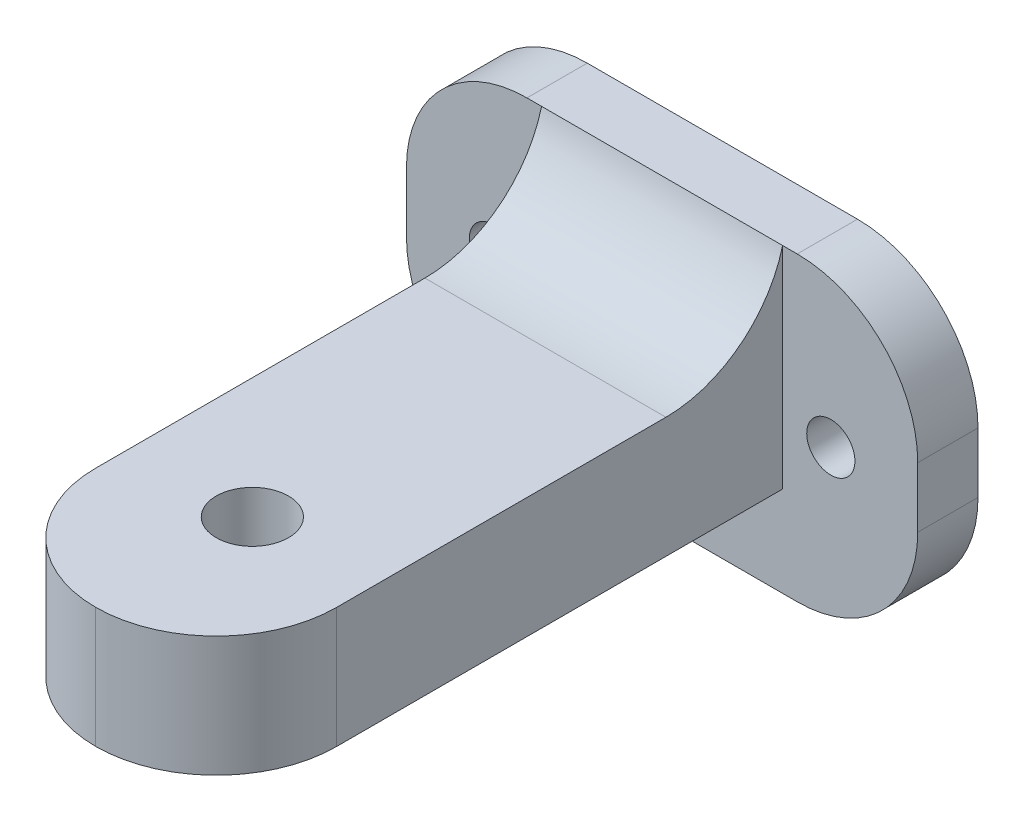
SolidWorks part; units mm, degrees
ref_plane "Front Plane" through (0, 0, 0) normal (0, 0, 1) x (1, 0, 0)
ref_plane "Top Plane" through (0, 0, 0) normal (0, 1, 0) x (1, 0, 0)
ref_plane "Right Plane" through (0, 0, 0) normal (1, 0, 0) x (0, 0, -1)
sketch "Sketch1" plane through (0, 0, 0) normal (0, 0, 1) x (1, 0, 0)
  line L0 (0, 8.9076) -> (0, -8.1671) construction
  line L2 (21.2128, -12.5) -> (-21.2128, -12.5)
  line L3 (21.2128, -12.5) -> (21.2128, 12.5)
  line L4 (21.2128, 12.5) -> (-21.2128, 12.5)
  line L5 (-21.2128, -12.5) -> (-21.2128, 12.5)
  line L6 (21.2128, -12.5) -> (-21.2128, 12.5) construction
  line L7 (21.2128, 12.5) -> (-21.2128, -12.5) construction
  circle A0 centre (-14, 0) radius 2
  circle A1 centre (14, 0) radius 2
  point P7 (0, 0)
  dimension "D1" = 4
  dimension "D2" = 14
  dimension "D3" = 25
  dimension "D4" = 12.5
extrude "Boss-Extrude1" add sketch "Sketch1" along normal blind 5
fillet "Fillet1" radius 10 4 edges at (-21.2128, -12.5, 2.5) (21.2128, -12.5, 2.5) (21.2128, 12.5, 2.5) (-21.2128, 12.5, 2.5)
sketch "Sketch2" plane through (0, 0, 5) normal (0, 0, 1) x (1, 0, 0)
  line L0 (0, 12.5) -> (0, -12.5) construction
  line L1 (11.2128, 12.5) -> (-11.2128, 12.5) construction
  line L2 (-11.2128, -12.5) -> (11.2128, -12.5) construction
  line L4 (10, -5) -> (-10, -5)
  line L5 (10, -5) -> (10, 5)
  line L6 (10, 5) -> (-10, 5)
  line L7 (-10, -5) -> (-10, 5)
  line L8 (10, -5) -> (-10, 5) construction
  line L9 (10, 5) -> (-10, -5) construction
  point P6 (0, 0)
  dimension "D1" = 20
  dimension "D2" = 10
extrude "Boss-Extrude2" add sketch "Sketch2" along normal blind 47
sketch "Sketch3" plane through (0, -5, 0) normal (0, -1, 0) x (1, 0, 0)
  line L0 (-10, 5) -> (10, 5) construction
  circle A0 centre (0, 39) radius 5.25
  dimension "D2" = 10.5
  dimension "D1" = 34
extrude "Cut-Extrude1" cut sketch "Sketch3" against normal blind 5
sketch "Sketch4" plane through (0, 0, 0) normal (0, -1, 0) x (1, 0, 0)
  circle A0 centre (0, 39) radius 3
  dimension "D1" = 6
extrude "Cut-Extrude2" cut sketch "Sketch4" against normal blind 5
fillet "Fillet2" radius 10 3 edges at (0, 5, 5) (-10, 0, 52) (10, 0, 52)
sketch "Sketch5" plane through (0, -5, 0) normal (0, -1, 0) x (1, 0, 0)
  line L0 (0, 5) -> (0, 33.75)
  line L1 (-10, 5) -> (10, 5) construction
  circle A0 centre (0, 39) radius 5.25 construction
